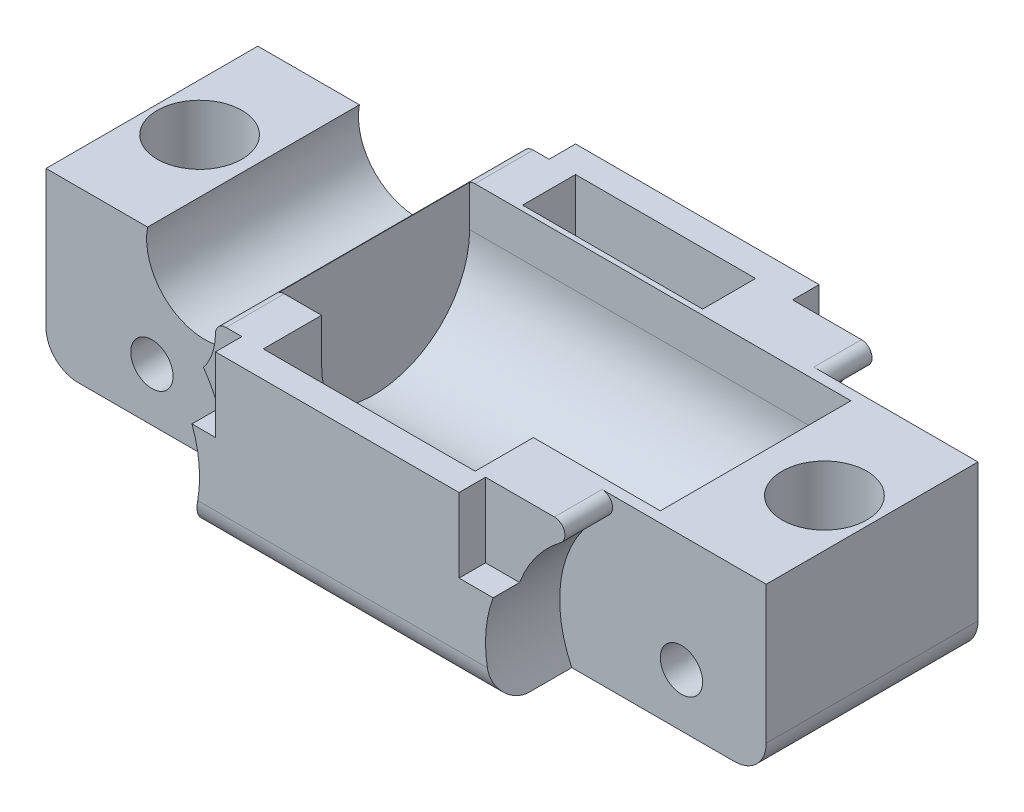
SolidWorks part; units mm, degrees
material "ABS"
ref_plane "Front Plane" through (0, 0, 0) normal (0, 0, 1) x (1, 0, 0)
ref_plane "Top Plane" through (0, 0, 0) normal (0, 1, 0) x (1, 0, 0)
ref_plane "Right Plane" through (0, 0, 0) normal (1, 0, 0) x (0, 0, -1)
sketch "Sketch1" plane through (0, 0, 0) normal (0, 1, 0) x (1, 0, 0)
  line L1 (-34, 17) -> (34, 17)
  line L2 (-34, 17) -> (-34, -17)
  line L3 (-34, -17) -> (34, -17)
  line L4 (34, 17) -> (34, -17)
  line L5 (-34, 17) -> (34, -17) construction
  line L6 (-34, -17) -> (34, 17) construction
  point P0 (0, 0)
  dimension "D1" = 68
  dimension "D2" = 34
extrude "Boss-Extrude1" add sketch "Sketch1" along normal blind 16
sketch "Sketch2" plane through (0, 0, 0) normal (0, 0, 1) x (1, 0, 0)
  point P0 (-24, 5)
  point P1 (26, 5)
  dimension "D1" = 50
  dimension "D2" = 26
  dimension "D3" = 5
sketch "Sketch3" plane through (0, 0, 0) normal (0, 0, 1) x (1, 0, 0)
  line L0 (26, 16.5) -> (37.5, 16.5)
  line L1 (37.5, 16.5) -> (37.5, 5)
  line L2 (37.5, 5) -> (37.5, -6.5)
  line L3 (37.5, -6.5) -> (26, -6.5)
  line L4 (-24, -6.5) -> (-35.5, -6.5)
  line L5 (-35.5, -6.5) -> (-35.5, 16.5)
  line L6 (-35.5, 16.5) -> (-24, 16.5)
  circle A0 centre (-24, 5) radius 11.5
  circle A1 centre (26, 5) radius 11.5
  dimension "D1" = 23
extrude "Cut-Extrude2" cut sketch "Sketch3" along normal blind 10 from offset 10 contours A1 L3 L2 | A1 | A1 L1 L0 | A0 | A0 L5 L4 | A0 L6 L5 region at (34.9313, 13.9313, 0) region at (26, 5, 0) region at (34.9313, -3.9313, 0) region at (-24, 5, 0) region at (-32.9313, -3.9313, 0) region at (-32.9313, 13.9313, 0)
mirror "Mirror1" about plane through (0, 0, 0) normal (0, 0, 1) of "Cut-Extrude2"
sketch "Sketch5" plane through (0, 0, 0) normal (0, 0, 1) x (1, 0, 0)
  circle A0 centre (26, 5) radius 2
  circle A1 centre (-24, 5) radius 2
  dimension "D1" = 4
extrude "Cut-Extrude3" cut sketch "Sketch5" against normal through all both and the other way through all
sketch "Sketch4" plane through (0, 0, 0) normal (1, 0, 0) x (0, 0, -1)
  line L0 (-9, 12) -> (-9, 23.0528)
  line L1 (-9, 23.0528) -> (9, 23.0528)
  line L2 (9, 23.0528) -> (9, 12)
  circle A0 centre (0, 12) radius 9
  dimension "D1" = 18
  dimension "D2" = 12
extrude "Battery" add sketch "Sketch4" along normal blind 23 and the other way blind 13 separate body contours A0 | A0 L2 L1 L0 region at (0, 17.5264, 8.7888) region at (0, 12, 0)
combine bodies "Combine1" operation type subtract main body 106 bodies to subtract 104
sketch "Sketch13" plane through (0, 16, 0) normal (0, 1, 0) x (1, 0, 0)
  circle A0 centre (29.5, 0) radius 4
  circle A1 centre (-29.5, 0) radius 4
  dimension "D1" = 8
  dimension "D3" = 5.5
  dimension "D2" = 3.5
extrude "MountHole" cut sketch "Sketch13" against normal blind 6
sketch "Sketch6" plane through (0, 0, 0) normal (0, 1, 0) x (1, 0, 0)
  line L1 (8.5, 9.5) -> (-8.5, 9.5)
  line L2 (8.5, 9.5) -> (8.5, 14.5)
  line L3 (8.5, 14.5) -> (-8.5, 14.5)
  line L4 (-8.5, 9.5) -> (-8.5, 14.5)
  line L5 (8.5, 9.5) -> (-8.5, 14.5) construction
  line L6 (8.5, 14.5) -> (-8.5, 9.5) construction
  point P0 (0, 12)
  dimension "D1" = 17
  dimension "D2" = 5
  dimension "D3" = 12
extrude "Charger" cut sketch "Sketch6" along normal up to next from offset 3
sketch "Sketch7" plane through (0, 0, 0) normal (0, -1, 0) x (1, 0, 0)
  line L1 (6, -16) -> (-6, -16)
  line L2 (6, -16) -> (6, -8)
  line L3 (6, -8) -> (-6, -8)
  line L4 (-6, -16) -> (-6, -8)
  line L5 (6, -16) -> (-6, -8) construction
  line L6 (6, -8) -> (-6, -16) construction
  point P0 (0, -12)
  dimension "D1" = 12
  dimension "D2" = 8
extrude "MicroUSB" cut sketch "Sketch7" against normal blind 3
fillet "Fillet1" radius 1.5 2 edges at (0, 3, -16) (0, 3, -8)
sketch "Sketch8" plane through (0, 0, 0) normal (0, 0, 1) x (1, 0, 0)
  circle A0 centre (-19, 15) radius 5.5
  dimension "D1" = 11
  dimension "D2" = 19
  dimension "D3" = 15
extrude "Motor" cut sketch "Sketch8" against normal through all both and the other way through all
fillet "BottomFillet_3mm" radius 3 4 edges at (1, 0, 17) (1, 0, -17) (34, 0, 0) (-34, 0, 0)
fillet "Fillet_1mm" radius 1 3 edges at (22.6459, 16, 13.5) (22.6459, 16, -13.5) (-13.5917, 16, 0)
sketch "Sketch10" plane through (0, 16, 0) normal (0, 1, 0) x (1, 0, 0)
  line L0 (-12.5, -17) -> (18.5, -17) construction
  line L1 (-8.983, -8.5) -> (11.017, -8.5)
  line L2 (-8.983, -8.5) -> (-8.983, -14.5)
  line L3 (-8.983, -14.5) -> (11.017, -14.5)
  line L4 (11.017, -8.5) -> (11.017, -14.5)
  line L5 (-8.983, -8.5) -> (11.017, -14.5) construction
  line L6 (-8.983, -14.5) -> (11.017, -8.5) construction
  point P0 (1.017, -11.5)
  dimension "D1" = 20
  dimension "D2" = 6
  dimension "D3" = 2.5
extrude "ControlBoard" cut sketch "Sketch10" against normal blind 12
fillet "Fillet2" radius 2 1 edges at (1.017, 9.042, 8.5)
hole_wizard "CSK for M3 Flat Head Machine Screw1" positions "Sketch11" profile "Sketch12" countersink size "M3" standard "ANSI Metric"
sketch "Sketch11" plane through (0, 0, 0) normal (0, -1, 0) x (-1, 0, 0)
  point P0 (-29.5, 0)
  point P5 (29.5, 0)
  point P8 (0, 0)
sketch "Sketch12" plane through (29.5, 0, 0) normal (1, 0, 0) x (0, 0, -1)
  line L0 (0, 0) -> (0, 11.0815)
  line L1 (0, 11.0815) -> (1.8, 10)
  line L2 (1.8, 10) -> (1.8, 1.35)
  line L3 (1.8, 1.35) -> (3.15, 0)
  line L5 (3.15, 0) -> (0, 0)
  line L6 (-1.8, 1.35) -> (-3.15, 0) construction
  line L10 (0, 11.0815) -> (-1.8, 10) construction
  line L11 (0, -6.35) -> (0, 107.95) construction
  dimension "Hole Dia." = 3.6
  dimension "Hole Depth" = 10
  dimension "Near C'Sink Dia." = 6.3
  dimension "Near C'Sink Angle" = 90
  dimension "Drill Angle" = 118
sketch "Sketch14" plane through (0, 0, 0) normal (0, 0, 1) x (1, 0, 0)
  line L1 (25.8393, 9) -> (12, 9)
  line L2 (25.8393, 9) -> (25.8393, 23.5989)
  line L3 (25.8393, 23.5989) -> (12, 23.5989)
  line L4 (12, 9) -> (12, 23.5989)
  line L5 (-22.7748, 9) -> (-11, 9)
  line L6 (-22.7748, 9) -> (-22.7748, 22.7145)
  line L7 (-22.7748, 22.7145) -> (-11, 22.7145)
  line L8 (-11, 9) -> (-11, 22.7145)
  dimension "D1" = 12
  dimension "D2" = 11
  dimension "D3" = 9
extrude "Cut-Extrude5" cut sketch "Sketch14" along normal blind 2.5 from vertex starting at point (18.5, 16, -17)
extrude "Cut-Extrude6" cut sketch "Sketch14<2>" against normal blind 2.5 from vertex starting at point (18.5, 16, 17)
sketch "Sketch14<2>" plane through (0, 0, 0) normal (0, 0, 1) x (1, 0, 0) same geometry as "Sketch14"
